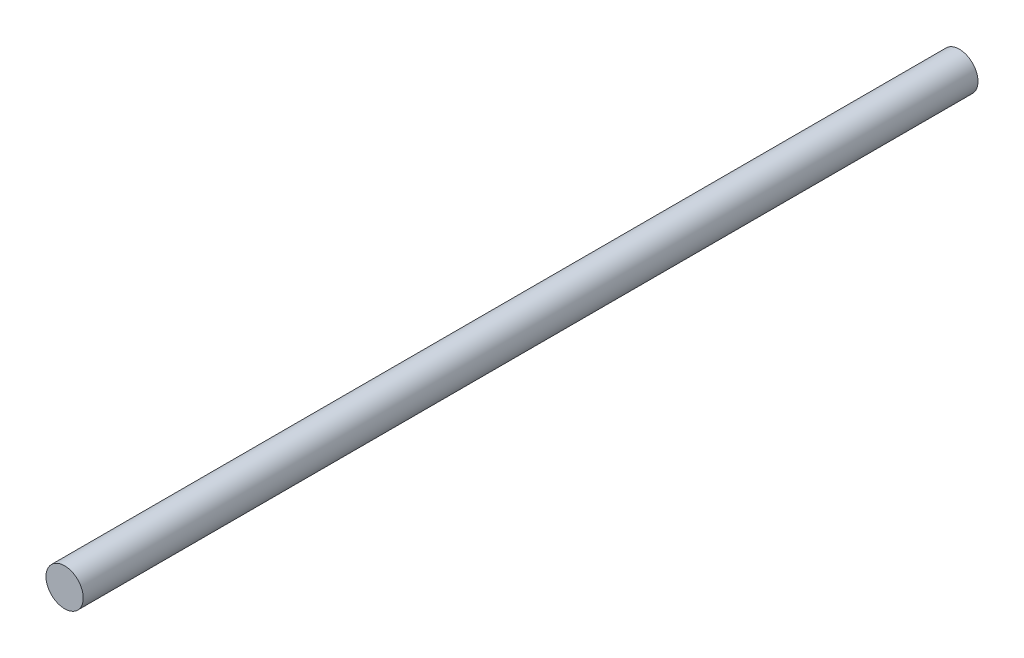
SolidWorks part; units mm, degrees
ref_plane "Front Plane" through (0, 0, 0) normal (0, 0, 1) x (1, 0, 0)
ref_plane "Top Plane" through (0, 0, 0) normal (0, 1, 0) x (1, 0, 0)
ref_plane "Right Plane" through (0, 0, 0) normal (1, 0, 0) x (0, 0, -1)
sketch "Sketch1" plane through (0, 0, 0) normal (0, 0, 1) x (1, 0, 0)
  line L1 (-19.05, 0) -> (19.05, 0) construction
  dimension "OD" = 38.1
sketch "Sketch2" plane through (0, 0, 0) normal (1, 0, 0) x (0, 0, -1)
  line L0 (304.8, 0) -> (-304.8, 0)
  point P4 (0, 0)
  dimension "Length" = 609.6
sketch "Sketch3" plane through (0, 0, 0) normal (0, 0, 1) x (1, 0, 0)
  circle A0 centre (0, 0) radius 19.05
extrude "Boss-Extrude1" add sketch "Sketch3" along normal blind 457.2 and the other way blind 457.2
